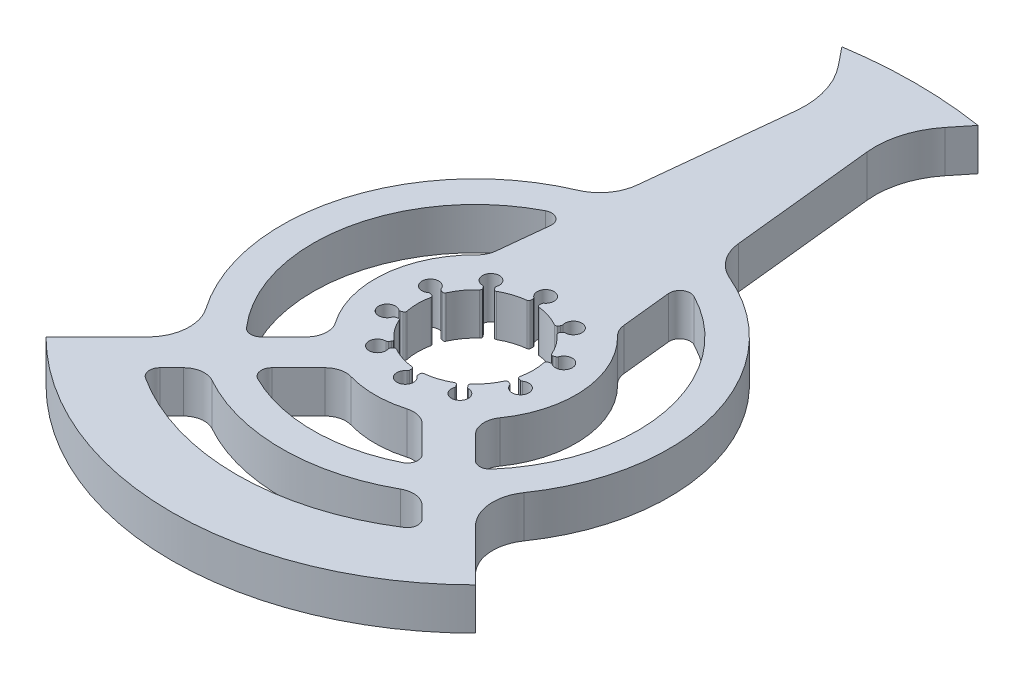
SolidWorks part; units mm, degrees
material "AISI Type A2 Tool Steel"
ref_plane "Front Plane" through (0, 0, 0) normal (0, 0, 1) x (1, 0, 0)
ref_plane "Top Plane" through (0, 0, 0) normal (0, 1, 0) x (1, 0, 0)
ref_plane "Right Plane" through (0, 0, 0) normal (1, 0, 0) x (0, 0, -1)
other "Center of Mass"
other "Bounding Box"
ref_plane "Default Plane" through (0, 2.286, 19.05) normal (0, -1, 0) x (-1, 0, 0)
sketch "Sketch1" plane through (0, 0, 0) normal (0, 1, 0) x (1, 0, 0)
  circle A0 centre (0, 0) radius 133.35 construction
  circle A1 centre (0, 0) radius 30.48
  circle A2 centre (0, 0) radius 17.4625
  dimension "D1" = 266.7
  dimension "D2" = 60.96
  dimension "D3" = 34.925
extrude "Boss-Extrude1" add sketch "Sketch1" along normal mid plane 12.7
sketch "Sketch2" plane through (0, 6.35, 0) normal (0, 1, 0) x (1, 0, 0)
  line L0 (-10.795, 107.95) -> (-19.6961, 23.2614)
  line L1 (19.6961, 23.2614) -> (10.795, 107.95)
  line L4 (0, 0) -> (0, 133.35) construction
  line L5 (-10.795, 107.95) -> (0, 107.95) construction
  line L6 (0, 107.95) -> (10.795, 107.95) construction
  line L7 (-20.6375, 131.7434) -> (0, 0) construction
  line L8 (-20.6375, 131.7434) -> (124.4119, -47.9991) construction
  line L9 (-20.6375, 131.7434) -> (-16.1956, 126.2391)
  line L10 (20.6375, 131.7434) -> (16.1956, 126.2391)
  circle A0 centre (0, 0) radius 133.35 construction
  circle A1 centre (0, 0) radius 133.35 construction
  arc A2 (-20.6375, 131.7434) -> (20.6375, 131.7434) centre (0, 0) cw
  circle A5 centre (0, 0) radius 30.48
  arc A6 (19.6961, 23.2614) -> (-19.6961, 23.2614) centre (0, 0) ccw
  arc A7 (-19.6961, 23.2614) -> (19.6961, 23.2614) centre (0, 0) ccw construction
  arc A9 (-16.1956, 126.2391) -> (-10.795, 107.95) centre (-35.6252, 110.5598) cw
  arc A10 (16.1956, 126.2391) -> (10.795, 107.95) centre (35.6252, 110.5598) ccw
  dimension "D3" = 41.275
  dimension "D4" = 25.4
  dimension "D5" = 6
  dimension "D6" = 10.795
  dimension "D1" = 30
  dimension "D2" = 0
extrude "Boss-Extrude2" add sketch "Sketch2" against normal through all
sketch "Sketch3" plane through (0, 6.35, 0) normal (0, 1, 0) x (1, 0, 0)
  line L0 (-65.1069, -65.1069) -> (-21.5526, -21.5526)
  line L1 (21.5526, -21.5526) -> (65.1069, -65.1069)
  line L2 (0, -30.48) -> (0, -92.075) construction
  line L4 (-21.5526, -21.5526) -> (0, 0) construction
  line L5 (0, 0) -> (21.5526, -21.5526) construction
  arc A0 (-65.1069, -65.1069) -> (65.1069, -65.1069) centre (0, 0) ccw
  circle A1 centre (0, 0) radius 30.48 construction
  arc A3 (-21.5526, -21.5526) -> (21.5526, -21.5526) centre (0, 0) ccw
  point P13 (0, -92.075)
  dimension "D2" = 92.075
  dimension "D1" = 90
extrude "Boss-Extrude3" add sketch "Sketch3" against normal through all
sketch "Sketch5" plane through (0, 6.35, 0) normal (0, 1, 0) x (1, 0, 0)
  line L0 (0, 17.4625) -> (0, 21.2725) construction
  line L2 (-1.27, 17.4163) -> (1.27, 17.4163)
  line L3 (-1.27, 17.4163) -> (-1.27, 19.0581)
  line L5 (1.27, 17.4163) -> (1.27, 19.0581)
  arc A0 (1.27, 19.0581) -> (-1.27, 19.0581) centre (0, 21.2725) ccw
  circle A1 centre (0, 0) radius 17.4625 construction
  circle A2 centre (0, 21.2725) radius 4.5847 construction
  arc A3 (1.27, 19.0581) -> (-1.27, 19.0581) centre (0, 21.2725) cw construction
  point P10 (0, 18.7198)
  dimension "D2" = 5.1054
  dimension "D4" = 9.1694
  dimension "D1" = 3.81
  dimension "D3" = 2.54
extrude "Cut-Extrude2" cut sketch "Sketch5" against normal through all
pattern_circular "CirPattern1" count 10 over 360 about axis through (0, 6.35, 0) along (0, -1, 0) of "Cut-Extrude2"
sketch "Sketch6" plane through (0, 6.35, 0) normal (0, 1, 0) x (1, 0, 0)
  circle A0 centre (0, 0) radius 17.526
  arc A1 (-11.2645, 13.3436) -> (-16.1714, 6.5898) centre (0, 0) ccw construction
  dimension "D1" = 0.0635
extrude "Cut-Extrude3" cut sketch "Sketch6" against normal through all
sketch "Sketch7" plane through (0, 6.35, 0) normal (0, 1, 0) x (1, 0, 0)
  line L0 (-42.454, -58.6185) -> (-11.8976, -28.062)
  line L1 (11.8976, -28.062) -> (42.454, -58.6185)
  line L3 (-21.5526, -21.5526) -> (-65.1069, -65.1069) construction
  line L4 (65.1069, -65.1069) -> (21.5526, -21.5526) construction
  line L5 (-42.454, -58.6185) -> (-50.5363, -50.5363) construction
  line L6 (42.454, -58.6185) -> (50.5363, -50.5363) construction
  arc A0 (-11.8976, -28.062) -> (11.8976, -28.062) centre (0, 0) ccw
  arc A1 (-42.454, -58.6185) -> (42.454, -58.6185) centre (0, 0) ccw
  arc A2 (-65.1069, -65.1069) -> (65.1069, -65.1069) centre (0, 0) ccw construction
  arc A4 (21.5526, -21.5526) -> (19.6961, 23.2614) centre (0, 0) ccw construction
  dimension "D1" = 19.6977
  dimension "D2" = 11.43
extrude "Cut-Extrude4" cut sketch "Sketch7" against normal through all
sketch "Sketch8" plane through (0, 6.35, 0) normal (0, 1, 0) x (1, 0, 0)
  circle A0 centre (0, 0) radius 49.2125
  circle A1 centre (0, 0) radius 58.7375
  dimension "D1" = 9.525
  dimension "D2" = 117.475
extrude "Boss-Extrude4" add sketch "Sketch8" against normal through all
sketch "Sketch11" plane through (0, 6.35, 0) normal (0, 1, 0) x (1, 0, 0)
  line L0 (-7.5441, 29.5316) -> (-5.5081, 48.9033)
  line L1 (5.5081, 48.9033) -> (7.5441, 29.5316)
  line L3 (-17.2986, 46.072) -> (-19.6961, 23.2614) construction
  line L4 (19.6961, 23.2614) -> (17.2986, 46.072) construction
  line L5 (-6.5261, 39.2174) -> (-17.8935, 40.4122) construction
  line L6 (6.5261, 39.2174) -> (17.8935, 40.4122) construction
  arc A0 (-7.5441, 29.5316) -> (7.5441, 29.5316) centre (0, 0) cw
  arc A1 (-5.5081, 48.9033) -> (5.5081, 48.9033) centre (0, 0) cw
  arc A2 (-19.6961, 23.2614) -> (-21.5526, -21.5526) centre (0, 0) ccw construction
  arc A3 (-17.2986, 46.072) -> (-34.7985, -34.7985) centre (0, 0) ccw construction
  dimension "D1" = 11.43
extrude "Cut-Extrude6" [suppressed] cut sketch "Sketch11" against normal through all
fillet "Fillet1" radius 6.35 8 edges at (-21.5526, 0, 21.5526) (21.5526, 0, 21.5526) (19.6961, 0, -23.2614) (-19.6961, 0, -23.2614) (11.8976, 0, 28.062) (-11.8976, 0, 28.062) (32.6575, 0, 48.8219) (-32.6575, 0, 48.8219)
fillet "Fillet6" radius 0.635 20 edges at (-11.3019, 0, -13.3951) (-16.2319, 0, -6.6094) (-17.0168, 0, -4.1938) (-17.0168, 0, 4.1938) (-16.2319, 0, 6.6094) (-11.3019, 0, 13.3951) (-9.247, 0, 14.888) (-1.27, 0, 17.4799) (1.27, 0, 17.4799) (9.247, 0, 14.888) (11.3019, 0, 13.3951) (16.2319, 0, 6.6094) (17.0168, 0, 4.1938) (17.0168, 0, -4.1938) (16.2319, 0, -6.6094) (11.3019, 0, -13.3951) (9.247, 0, -14.888) (1.27, 0, -17.4799) (-1.27, 0, -17.4799) (-9.247, 0, -14.888)
fillet "Fillet7" radius 3.175 8 edges at (-25.7647, 0, 41.9291) (25.7647, 0, 41.9291) (34.7985, 0, 34.7985) (-34.7985, 0, 34.7985) (-17.2986, 0, -46.072) (17.2986, 0, -46.072) (42.454, 0, 58.6185) (-42.454, 0, 58.6185)
fillet "Fillet8" radius 12.7 4 edges at (-16.2071, 0, -56.4573) (16.2071, 0, -56.4573) (41.5337, 0, 41.5337) (-41.5337, 0, 41.5337)
fillet "Fillet9" [suppressed] radius 3.175
sketch "Sketch12" plane through (0, -6.35, 0) normal (0, -1, 0) x (1, 0, 0)
  line L0 (-58.7375, 0) -> (-53.975, 0) construction
  line L1 (-53.975, 0) -> (-49.2125, 0) construction
  circle A0 centre (0, 0) radius 53.975
  arc A1 (-48.2558, 33.4883) -> (-23.0251, -54.0365) centre (0, 0) ccw construction
  arc A2 (-37.1155, 32.3157) -> (-22.4793, -43.7784) centre (0, 0) ccw construction
fillet "Fillet10" radius 0.635 20 edges at (-12.2295, 0, -14.6719) (-10.1746, 0, -16.1648) (-18.5178, 0, -4.6814) (-17.7329, 0, -7.0971) (-18.5178, 0, 4.6814) (-17.7329, 0, 7.0971) (-10.1746, 0, 16.1648) (-12.2295, 0, 14.6719) (-1.27, 0, 19.0581) (1.27, 0, 19.0581) (12.2295, 0, 14.6719) (10.1746, 0, 16.1648) (17.7329, 0, 7.0971) (18.5178, 0, 4.6814) (18.5178, 0, -4.6814) (17.7329, 0, -7.0971) (12.2295, 0, -14.6719) (10.1746, 0, -16.1648) (-1.27, 0, -19.0581) (1.27, 0, -19.0581)
equation "\"Unit Measure\"= \"BoundingVolume\" / \"Thickness\"'in^2"
